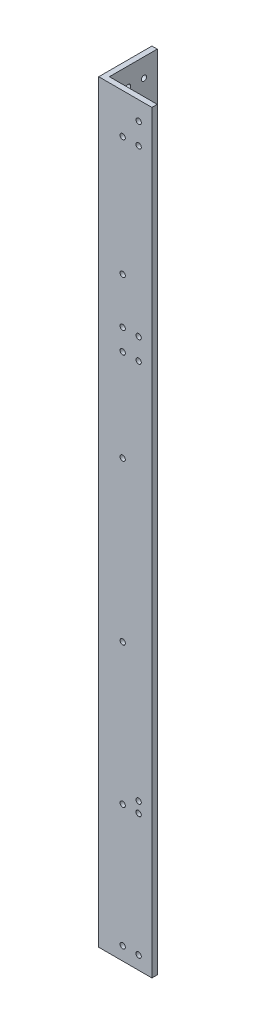
SolidWorks part; units mm, degrees
ref_plane "Front Plane" through (0, 0, 0) normal (0, 0, 1) x (1, 0, 0)
ref_plane "Top Plane" through (0, 0, 0) normal (0, 1, 0) x (1, 0, 0)
ref_plane "Right Plane" through (0, 0, 0) normal (1, 0, 0) x (0, 0, -1)
sketch "Sketch2" plane through (0, 0, 0) normal (0, 1, 0) x (1, 0, 0)
  line L0 (0, 31.75) -> (3.175, 31.75)
  line L1 (3.175, 31.75) -> (3.175, 3.175)
  line L2 (3.175, 3.175) -> (31.75, 3.175)
  line L3 (31.75, 3.175) -> (31.75, 0)
  line L4 (31.75, 0) -> (0, 0)
  line L5 (0, 0) -> (0, 31.75)
  point P9 (1.5875, 31.75)
  point P10 (31.75, 1.5875)
  dimension "D4" = 3.175
  dimension "D1" = 31.75
  dimension "D2" = 31.75
  dimension "D3" = 3.175
extrude "Boss-Extrude1" add sketch "Sketch2" along normal blind 450
sketch "LeftSideHoles-Sketch3" plane through (0, 0, 0) normal (0, 0, 1) x (1, 0, 0)
  line L0 (0, 0) -> (31.75, 0) construction
  line L1 (0, 450) -> (31.75, 450) construction
  line L3 (0, 450) -> (0, 0) construction
  circle A0 centre (14.2875, 81.1125) radius 1.5875
  circle A1 centre (23.8125, 81.1125) radius 1.5875
  circle A3 centre (23.8125, 87.4625) radius 1.5875
  circle A5 centre (14.2875, 426.1875) radius 1.5875
  circle A6 centre (23.8125, 438.8875) radius 1.5875
  circle A7 centre (23.8125, 426.1875) radius 1.5875
  circle A10 centre (14.2875, 327.6026) radius 1.5875
  circle A11 centre (23.8125, 327.6026) radius 1.5875
  circle A12 centre (14.2875, 314.9026) radius 1.5875
  circle A13 centre (23.8125, 314.9026) radius 1.5875
  circle A14 centre (14.2875, 7.9375) radius 1.5875
  circle A15 centre (23.8125, 7.9375) radius 1.5875
  circle A16 centre (14.2875, 165) radius 1.5875
  circle A17 centre (14.2875, 260) radius 1.5875
  circle A18 centre (14.2875, 355) radius 1.5875
  point P24 (15.875, 0)
  dimension "D4" = 3.175
  dimension "D1" = 81.1125
  dimension "D2" = 14.2875
  dimension "D10" = 7.9375
  dimension "D7" = 12.7
  dimension "D3" = 9.525
  dimension "D11" = 327.6026
  dimension "D12" = 165
  dimension "D13" = 95
  dimension "D14" = 95
  dimension "D5" = 6.35
  dimension "D6" = 12.7
  dimension "D8" = 11.1125
sketch "BackSideHoles-Sketch4" plane through (0, 0, 0) normal (-1, 0, 0) x (0, 0, 1)
  line L0 (-31.75, 450) -> (0, 450) construction
  line L2 (0, 450) -> (0, 0) construction
  line L3 (-31.75, 0) -> (0, 0) construction
  circle A0 centre (-23.8125, 81.1125) radius 1.5875
  circle A2 centre (-23.8125, 87.4625) radius 1.5875
  circle A3 centre (-14.2875, 87.4625) radius 1.5875
  circle A4 centre (-23.8125, 438.8875) radius 1.5875
  circle A5 centre (-14.2875, 438.8875) radius 1.5875
  circle A6 centre (-23.8125, 426.1875) radius 1.5875
  circle A10 centre (-23.8125, 327.6026) radius 1.5875
  circle A11 centre (-14.2875, 327.6026) radius 1.5875
  circle A12 centre (-23.8125, 321.2526) radius 1.5875
  circle A13 centre (-14.2875, 321.2526) radius 1.5875
  circle A14 centre (-14.2875, 165) radius 1.5875
  circle A15 centre (-14.2875, 260) radius 1.5875
  circle A16 centre (-14.2875, 355) radius 1.5875
  circle A17 centre (-23.8125, 7.9375) radius 1.5875
  circle A18 centre (-14.2875, 7.9375) radius 1.5875
  dimension "D4" = 3.175
  dimension "D2" = 14.2875
  dimension "D7" = 12.7
  dimension "D5" = 6.35
  dimension "D6" = 11.1125
  dimension "D8" = 6.35
  dimension "D1" = 327.6026
  dimension "D10" = 165
  dimension "D11" = 95
  dimension "D12" = 95
  dimension "D13" = 7.9375
  dimension "D3" = 81.1125
  dimension "D9" = 9.525
extrude "LeftSideHoles-Cut-Extrude1" cut sketch "LeftSideHoles-Sketch3" against normal blind 3.175
extrude "BackSideHoles-Cut-Extrude2" cut sketch "BackSideHoles-Sketch4" against normal blind 3.175
equation "\"RailThickness\"= .125in'Spec"
equation "\"VSWidth\"= 1.25in'Spec"
equation "\"VSHeight\"= 1.25in'Spec"
equation "\"VSLength\"= 450mm"
equation "\"HoleOffsetFromEdge\"= \"RailThickness\" * 2.5"
equation "\"HoleOffsetFromSide\"= \"RailThickness\" * 3.5"
equation "\"LegHeight\"= 70mm'Space needed for PSU/Stepper/Electronics"
equation "\"VSBottomSideRailHoleY1FromBottomOfLowerRail\"= \"V1 BottomOfLowerRail\" + \"HoleOffsetFromSide\"'Equals 70.1125"
equation "\"VSSideRailHoleX1FromSide\"= \"HoleOffsetFromSide\" + \"RailThickness\""
equation "\"FasteningHoleDiameter\"= .125in"
equation "\"VSBottomSideRailHoleY2FromY1\"= \"LowerRailHeight\" - \"HoleOffsetFromSide\" - \"HoleOffsetFromEdge\"'Equals 6.35"
equation "\"VSTopSideRailHoleY1FromEdge\"= \"HoleOffsetFromEdge\" + \"RailThickness\""
equation "\"D4@LeftSideHoles-Sketch3\"=\"FasteningHoleDiameter\""
equation "\"D1@LeftSideHoles-Sketch3\"=\"VSBottomSideRailHoleY1FromBottomOfLowerRail\""
equation "\"D2@LeftSideHoles-Sketch3\"=\"VSSideRailHoleX1FromSide\""
equation "\"D1@Boss-Extrude1\"=\"VSLength\""
equation "\"D4@BackSideHoles-Sketch4\" = \"FasteningHoleDiameter\""
equation "\"VSMidSideRailHoleY1FromV8TopOfMidSideRail\"= \"V8 ToTopOfMidSideRail\" - \"HoleOffsetFromEdge\"'Equals 308.2875"
equation "\"LowerRailHeight\"= 1.00in"
equation "\"D1@Sketch2\"=\"VSHeight\""
equation "\"D2@Sketch2\"=\"VSWidth\""
equation "\"MidBackRailHeight\"= 1.00in"
equation "\"VSMidBackRailHoleY1FromV7TopOfMidBackRail\"= \"V7 ToTopOfMidBackRail\" - \"HoleOffsetFromSide\"'Equals 308.2875"
equation "\"TopRailHeight\"= 1.25in"
equation "\"MidSideRailHeight\"= 1.25in"
equation "\"D10@LeftSideHoles-Sketch3\"=\"HoleOffsetFromEdge\""
equation "\"VSMidBackRailHoleY2FromY1\"= \"MidBackRailHeight\" - \"HoleOffsetFromSide\" - \"HoleOffsetFromEdge\"'Equals 6.35"
equation "\"VSMidSideRailHoleY2FromY1\"= \"MidSideRailHeight\" - \"HoleOffsetFromSide\" - \"HoleOffsetFromEdge\"'Equals 12.7"
equation "\"D7@LeftSideHoles-Sketch3\"=\"VSMidSideRailHoleY2FromY1\""
equation "\"D8@BackSideHoles-Sketch4\"=\"VSMidBackRailHoleY2FromY1\""
equation "\"D6@BackSideHoles-Sketch4\"=\"VSTopSideRailHoleY1FromEdge\""
equation "\"VSTopSideRailHoleY2FromY1\"= \"TopRailHeight\" - \"VSTopSideRailHoleY1FromEdge\" - \"HoleOffsetFromEdge\"'Equals 12.7"
equation "\"D7@BackSideHoles-Sketch4\"=\"VSTopSideRailHoleY2FromY1\""
equation "\"VSBottomSideRailHoleX2FromX1\"= \"VSWidth\" - \"VSSideRailHoleX1FromSide\" - \"HoleOffsetFromEdge\""
equation "\"D3@LeftSideHoles-Sketch3\"=\"VSBottomSideRailHoleX2FromX1\""
equation "\"V1 BottomOfLowerRail\"= \"LegHeight\""
equation "\"StepperShaftLength\"= 24mm'Pulley will be attached to the end"
equation "\"ZAxisLeadScrewLength\"= 200mm"
equation "\"LM8UUHeight\"= 24mm'Spec"
equation "\"V2 ToBedAtTopOfZAxis\" = \"V1 BottomOfLowerRail\" - \"LowerEnclosureThickness\" + \"StepperShaftLength\" + \"ZAxisLeadScrewLength\" - \"LM8UUHeight\" / 2"
equation "\"HotEndToTopOfXAxisGB\"= 63.315144mm'Measured from the100.Should be 63.315144"
equation "\"TopOfGBToBottomOfLinearRail\"= \"LinearGBWidth\" / 2 + \"LinearRailWidth\" / 2"
equation "\"LinearGBWidth\"= 27mm'Spec"
equation "\"V5 ToBottomOfXAxisLinearRail\"= \"V4 ToTopOfBuildPlate/HotEndTip\" + \"HotEndToTopOfXAxisGB\" - \"TopOfGBToBottomOfLinearRail\""
equation "\"LinearRailWidth\"= 12mm'Spec"
equation "\"V6 ToBottomOfGantryPulley\"= \"V5 ToBottomOfXAxisLinearRail\" - \"DistanceFromGABTopToLowerPulley\""
equation "\"GABUpperHeight\"= 6mm"
equation "\"GABMidWallHeight\"= 28mm'Must equal 28 or changes alignment"
equation "\"20TGT2PulleyWidth\"= 8.7mm'The STL of the Pulley in the diagram is a bit larger"
equation "\"GABMidShortRiserHeight\"= \"GABMidWallHeight\" / 2 - \"20TGT2PulleyWidth\"'Equals 5.3"
equation "\"GABRiserBossOffset\"= 0.8mm'Aligns Pulleys"
equation "\"DistanceFromGABTopToLowerPulley\"= \"GABUpperHeight\" + \"GABMidWallHeight\" - \"GABMidShortRiserHeight\" + \"GABRiserBossOffset\" / 2"
equation "\"V7 ToTopOfMidBackRail\"= \"V6 ToBottomOfGantryPulley\" + \"StepperShaftLength\""
equation "\"D1@BackSideHoles-Sketch4\" = \"VSMidBackRailHoleY1FromV7TopOfMidBackRail\""
equation "\"D11@LeftSideHoles-Sketch3\"=\"VSMidSideRailHoleY1FromV8TopOfMidSideRail\""
equation "\"V4 ToTopOfBuildPlate/HotEndTip\" = \"V2 ToBedAtTopOfZAxis\" + \"BedToBuildPlateStandoffLength\" + \"BuildPlateHeight\""
equation "\"BedToBuildPlateStandoffLength\"= 15mm"
equation "\"BuildPlateHeight\"= 8mm'Spec"
equation "\"V8 ToTopOfMidSideRail\"= \"V7 ToTopOfMidBackRail\" - \"RailThickness\""
equation "\"VSEnclosureOffsets\"= ( \"VSLength\" - \"LegHeight\" ) / 4"
equation "\"D12@LeftSideHoles-Sketch3\"=\"LegHeight\" + \"VSEnclosureOffsets\""
equation "\"D13@LeftSideHoles-Sketch3\"=\"VSEnclosureOffsets\""
equation "\"D14@LeftSideHoles-Sketch3\"=\"VSEnclosureOffsets\""
equation "\"D10@BackSideHoles-Sketch4\"=\"LegHeight\" + \"VSEnclosureOffsets\""
equation "\"D11@BackSideHoles-Sketch4\"=\"VSEnclosureOffsets\""
equation "\"D12@BackSideHoles-Sketch4\"=\"VSEnclosureOffsets\""
equation "\"D13@BackSideHoles-Sketch4\"=\"HoleOffsetFromEdge\""
equation "\"D5@BackSideHoles-Sketch4\"=\"VSBottomSideRailHoleY2FromY1\""
equation "\"D3@BackSideHoles-Sketch4\"=\"VSBottomSideRailHoleY1FromBottomOfLowerRail\""
equation "\"D2@BackSideHoles-Sketch4\"=\"VSSideRailHoleX1FromSide\""
equation "\"D5@LeftSideHoles-Sketch3\"=\"VSBottomSideRailHoleY2FromY1\""
equation "\"D6@LeftSideHoles-Sketch3\"=\"VSTopSideRailHoleY2FromY1\""
equation "\"D8@LeftSideHoles-Sketch3\"=\"VSTopSideRailHoleY1FromEdge\""
equation "\"LowerEnclosureThickness\"= 5mm"
